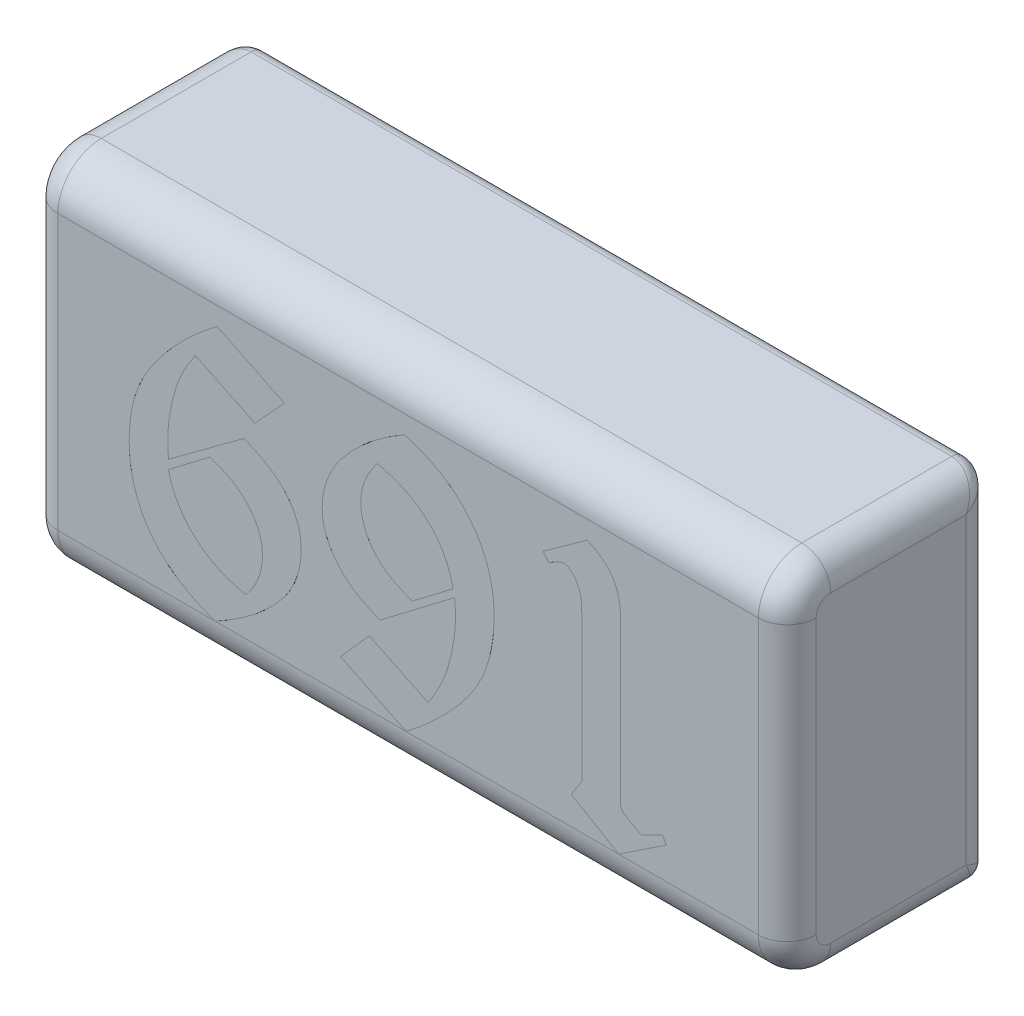
SolidWorks part; units mm, degrees
material "Polyurethane Foam Rigid"
ref_plane "Front Plane" through (0, 0, 0) normal (0, 0, 1) x (1, 0, 0)
ref_plane "Top Plane" through (0, 0, 0) normal (0, 1, 0) x (1, 0, 0)
ref_plane "Right Plane" through (0, 0, 0) normal (1, 0, 0) x (0, 0, -1)
sketch "Sketch1" plane through (0, 0, 0) normal (1, 0, 0) x (0, 0, -1)
  line L0 (0, 63.5) -> (-57.785, 63.5)
  line L1 (0, -63.5) -> (-9.525, -63.5) construction
  line L2 (0, -63.5) -> (0, 63.5)
  line L3 (0, 63.5) -> (-9.525, 63.5) construction
  line L4 (-9.525, -63.5) -> (-9.525, 63.5) construction
  line L6 (-73.025, 48.26) -> (-73.025, -48.26)
  line L8 (-57.785, -63.5) -> (0, -63.5)
  circle A0 centre (-41.275, 31.75) radius 31.75 construction
  circle A1 centre (-41.275, -31.75) radius 31.75 construction
  arc A2 (-73.025, -48.26) -> (-57.785, -63.5) centre (-57.785, -48.26) ccw
  arc A3 (-73.025, 48.26) -> (-57.785, 63.5) centre (-57.785, 48.26) cw
  dimension "D3" = 15.24
  dimension "D4" = 15.24
  dimension "D1" = 9.525
  dimension "D2" = 127
extrude "Boss-Extrude1" add sketch "Sketch1" along normal blind 266.7
fillet "Fillet1" radius 10.16 12 edges at (0, 0, 0) (0, 63.5, 28.8925) (0, 59.0363, 68.5613) (0, 0, 73.025) (0, -59.0363, 68.5613) (0, -63.5, 28.8925) (266.7, -59.0363, 68.5613) (266.7, 0, 73.025) (266.7, 59.0363, 68.5613) (266.7, 63.5, 28.8925) (266.7, 0, 0) (266.7, -63.5, 28.8925)
fillet "Fillet2" radius 5.08 6 edges at (263.7242, 60.5242, 2.9758) (2.9758, 60.5242, 2.9758) (263.7242, -60.5242, 2.9758) (2.9758, -60.5242, 2.9758) (133.35, 63.5, 0) (133.35, -63.5, 0)
sketch "Sketch2" plane through (0, 0, 73.025) normal (0, 0, 1) x (1, 0, 0)
  text T0 "691" font "Old English Text MT" height in points 400
extrude "Boss-Extrude2" add sketch "Sketch2" along normal blind 0.0003
